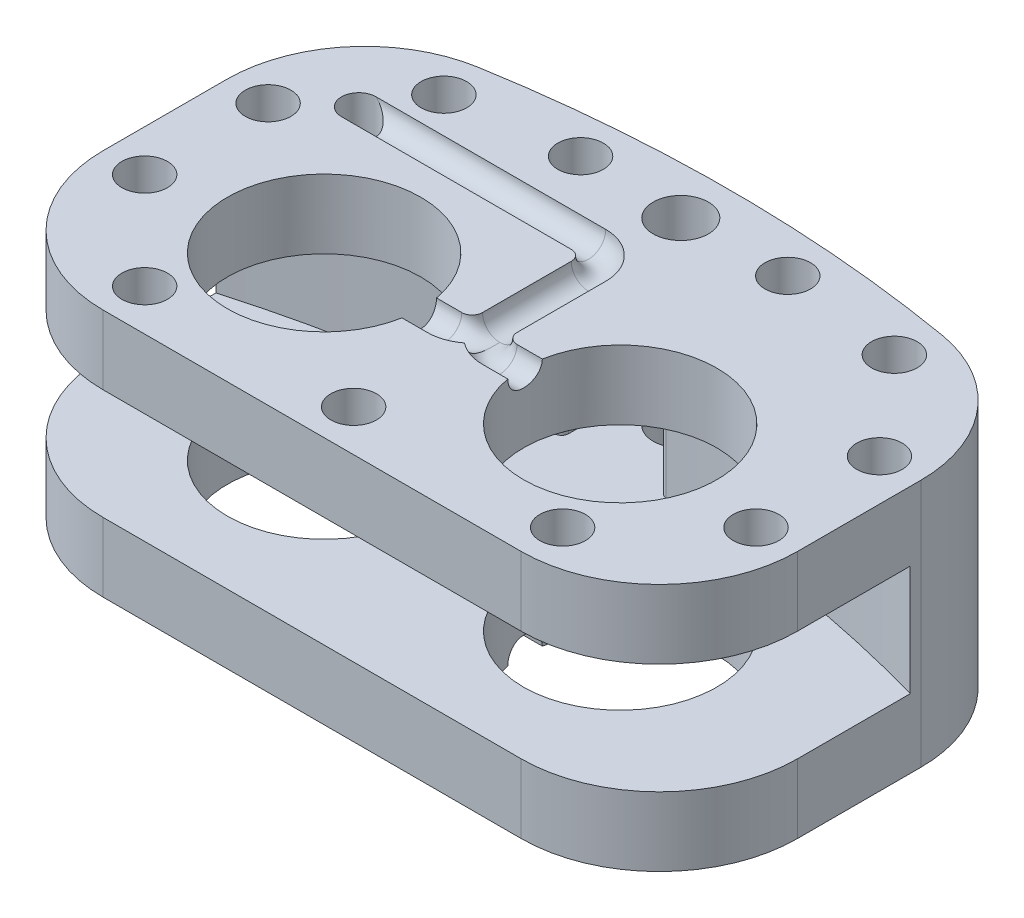
SolidWorks part; units mm, degrees
material "Plain Carbon Steel"
ref_plane "Front Plane" through (0, 0, 0) normal (0, 0, 1) x (1, 0, 0)
ref_plane "Top Plane" through (0, 0, 0) normal (0, 1, 0) x (1, 0, 0)
ref_plane "Right Plane" through (0, 0, 0) normal (1, 0, 0) x (0, 0, -1)
sketch "Sketch1" plane through (0, 0, 0) normal (0, 1, 0) x (1, 0, 0)
  line L0 (0, 0) -> (0, 99.9694) construction
  line L1 (-23.2937, 86.9333) -> (-19.2044, 71.6717) construction
  line L2 (23.2937, 86.9333) -> (19.2044, 71.6717) construction
  line L3 (-25.1276, 87.9821) -> (-20.261, 69.8196) construction
  line L4 (25.1276, 87.9821) -> (20.261, 69.8196) construction
  line L5 (2.4998, 91.4658) -> (2.4998, 94) construction
  line L6 (-2.5, 91.4658) -> (-2.5, 94.0002) construction
  circle A0 centre (0, 0) radius 90 construction
  circle A1 centre (0, 0) radius 74.2 construction
  arc A2 (23.2937, 86.9333) -> (-23.2937, 86.9333) centre (0, 0) ccw construction
  arc A3 (19.2044, 71.6717) -> (-19.2044, 71.6717) centre (0, 0) ccw construction
  arc A4 (25.1276, 87.9821) -> (2.4998, 91.4658) centre (0, 0) ccw construction
  arc A5 (20.261, 69.8196) -> (-20.261, 69.8196) centre (0, 0) ccw construction
  arc A6 (2.4998, 94) -> (-2.5, 94.0002) centre (0, 96.5) ccw construction
  arc A7 (-2.5, 91.4658) -> (-25.1276, 87.9821) centre (0, 0) ccw construction
  arc A8 (25.1276, 87.9821) -> (-25.1276, 87.9821) centre (0, 0) ccw construction
  circle A9 centre (0, 0) radius 91.5 construction
  point P7 (0, 74.2)
  point P18 (0, 91.5)
  point P26 (0, 96.5)
  dimension "D1" = 180
  dimension "D2" = 148.4
  dimension "D5" = 2.5
  dimension "D3" = 15
  dimension "D6" = 2.5
  dimension "D7" = 2.5
  dimension "D8" = 5
  dimension "D4" = 1.5
sketch "Sketch2" plane through (0, 0, 0) normal (0, 1, 0) x (1, 0, 0)
  line L1 (-25.1276, 69.8196) -> (25.1276, 69.8196)
  line L4 (25.1276, 96.8281) -> (25.1276, 69.8196)
  line L5 (-25.1276, 96.8281) -> (-25.1276, 69.8196)
  circle A1 centre (0, 0) radius 100.0354 construction
  arc A4 (2.4998, 94) -> (-2.5, 94.0002) centre (0, 96.5) ccw construction
  arc A5 (-25.1276, 96.8281) -> (25.1276, 96.8281) centre (0, 0) cw
  point P5 (0.0002, 100.0354)
extrude "Boss-Extrude1" add sketch "Sketch2" along normal blind 5
sketch "Sketch3" plane through (0, 5, 0) normal (0, 1, 0) x (1, 0, 0)
  line L0 (-11.7474, 89.23) -> (-9.685, 73.5652) construction
  line L1 (0, -200000) -> (0, 200099.9694) construction
  line L3 (0, -105.3445) -> (0, 105.3445) construction
  circle A0 centre (-10.7162, 81.3976) radius 6.9 construction
  circle A1 centre (0, 0) radius 74.2 construction
  circle A2 centre (0, 0) radius 90 construction
  circle A3 centre (10.7162, 81.3976) radius 6.9 construction
  point P9 (-9.8156, 74.5567)
  point P12 (-9.685, 73.5652)
  point P16 (-11.6168, 88.2386)
  dimension "D1" = 7.5
  dimension "D2" = 1
  dimension "D3" = 1
sketch "Sketch4" plane through (0, 5, 0) normal (0, 1, 0) x (1, 0, 0)
  point P0 (-10.7162, 81.3976)
  point P3 (10.7162, 81.3976)
hole_wizard "Ø12.0mm Dowel Hole1" positions "Sketch4" profile "Sketch5" hole size "Ø12.0" standard "ANSI Metric" end condition through all
sketch "Sketch5" plane through (-10.7162, 5, -81.3976) normal (1, 0, 0) x (0, 0, 1)
  line L0 (0, 0) -> (0, 5)
  line L1 (0, 5) -> (7, 5)
  line L2 (7, 5) -> (7, 0)
  line L5 (7, 0) -> (0, 0)
  line L11 (0, -6.35) -> (0, 107.95) construction
  dimension "Thru Hole Dia." = 14
  dimension "Thru Hole Depth" = 5
sketch "Sketch6" plane through (0, 5, 0) normal (0, 1, 0) x (1, 0, 0)
  line L0 (-3.5354, 91.4317) -> (-3.5354, 99.9729)
  line L1 (3.5354, 91.4317) -> (3.5354, 99.9729)
  line L2 (25.1276, 87.9821) -> (25.1276, 96.8281)
  line L3 (-25.1276, 87.9821) -> (-25.1276, 96.8281)
  arc A0 (-2.5, 91.4658) -> (-25.1276, 87.9821) centre (0, 0) ccw construction
  arc A1 (25.1276, 96.8281) -> (-25.1276, 96.8281) centre (0, 0) ccw construction
  arc A2 (25.1276, 87.9821) -> (2.4998, 91.4658) centre (0, 0) ccw construction
  arc A3 (2.4998, 94) -> (-2.5, 94.0002) centre (0, 96.5) ccw construction
  arc A4 (-25.1276, 96.8281) -> (-3.5354, 99.9729) centre (0, 0) cw
  arc A5 (3.5354, 99.9729) -> (25.1276, 96.8281) centre (0, 0) cw
  arc A6 (-25.1276, 87.9821) -> (-3.5354, 91.4317) centre (0, 0) cw
  arc A7 (3.5354, 91.4317) -> (25.1276, 87.9821) centre (0, 0) cw
extrude "Boss-Extrude2" add sketch "Sketch6" along normal blind 4
sketch "Sketch7" plane through (0, 5, 0) normal (0, 1, 0) x (1, 0, 0)
  point P0 (0, 96.5)
hole_wizard "Ø4.0mm Dowel Hole1" positions "Sketch7" profile "Sketch8" hole size "Ø4.0" standard "ANSI Metric" end condition through all
sketch "Sketch8" plane through (0, 5, -96.5) normal (1, 0, 0) x (0, 0, 1)
  line L0 (0, 0) -> (0, 5)
  line L1 (0, 5) -> (2, 5)
  line L2 (2, 5) -> (2, 0)
  line L5 (2, 0) -> (0, 0)
  line L11 (0, -6.35) -> (0, 107.95) construction
  dimension "Thru Hole Dia." = 4
  dimension "Thru Hole Depth" = 5
sketch "Sketch9" plane through (0, 0, 0) normal (0, -1, 0) x (1, 0, 0)
  line L0 (-2, -81.3976) -> (-10.7162, -81.3976)
  line L1 (0, -83.3976) -> (0, -89.8196)
  line L2 (-2, -91.8196) -> (-18.6276, -91.8196)
  line L4 (-25.1276, -69.8196) -> (25.1276, -69.8196) construction
  line L5 (-25.1276, -96.8281) -> (-25.1276, -69.8196) construction
  arc A0 (0, -89.8196) -> (-2, -91.8196) centre (-2, -89.8196) cw
  arc A1 (0, -83.3976) -> (-2, -81.3976) centre (-2, -83.3976) ccw
  point P4 (10.7162, -81.3976)
  point P11 (-10.7162, -81.3976)
  dimension "D3" = 2
  dimension "D1" = 22
  dimension "D2" = 6.5
sketch3d "3DSketch1"
  line L0 (-18.6276, 0, -91.8196) -> (-2, 0, -91.8196)
  line L1 (0, 0, -89.8196) -> (0, 0, -83.3976)
  line L2 (2, 0, -81.3976) -> (10.7162, 0, -81.3976)
  line L3 (0, 0, -83.3976) -> (0, 0, -89.8196) construction
  line L4 (-18.6276, 0, -91.8196) -> (-18.6276, 9, -91.8196)
  line L5 (-18.6276, 9, -91.8196) -> (-25.1276, 9, -96.8281)
  arc A0 (0, 0, -83.3976) -> (2, 0, -81.3976) centre (2, 0, -83.3976) ccw
  arc A1 (-2, 0, -91.8196) -> (0, 0, -89.8196) centre (-2, 0, -89.8196) ccw
  point P0 (-13.6276, 0, -91.8196)
  point P14 (0, 0, -81.3976)
  point P15 (2, 2, -83.3976)
  point P18 (0, 0, -91.8196)
  point P19 (-2, -2, -89.8196)
  dimension "D1" = 2
  dimension "D2" = 5
ref_plane "Plane3" through (-13.6276, 0, 0) normal (1, 0, 0) x (0, 0, -1)
sketch "Sketch13" plane through (-13.6276, 0, 0) normal (1, 0, 0) x (0, 0, -1)
  line L1 (83.3976, 0) -> (89.8196, 0) construction
  line L2 (69.8196, 0) -> (96.8281, 0) construction
  circle A0 centre (91.8196, 0) radius 1.25
  point P8 (91.8196, 0)
  dimension "D1" = 2.5
sweep "Cut-Sweep6" cut profiles "Sketch13" path "3DSketch1"
sweep "Cut-Sweep7" cut profiles "Sketch13<4>" path "Sketch9"
sketch "Sketch13<4>" plane through (-13.6276, 0, 0) normal (1, 0, 0) x (0, 0, -1) same geometry as "Sketch13"
ref_plane "Plane2" through (0, 9, 0) normal (0, 1, 0) x (1, 0, 0)
mirror "Mirror5" about plane through (0, 9, 0) normal (0, 1, 0) of "Boss-Extrude2"
mirror "Mirror6" about plane through (0, 9, 0) normal (0, 1, 0) of "Ø4.0mm Dowel Hole1", "Ø12.0mm Dowel Hole1", "Boss-Extrude1", "Cut-Sweep7", "Cut-Sweep6"
ref_plane "Plane4" through (-25.1276, 9, -96.8281) normal (-0.7921, 0, -0.6104) x (-0.6104, 0, 0.7921)
sketch "Sketch16" plane through (-25.1276, 9, -96.8281) normal (-0.7921, 0, -0.6104) x (-0.6104, 0, 0.7921)
  point P0 (0, 0)
hole_wizard "M4x0.7 Tapped Hole2" positions "Sketch16" profile "Sketch17" tap size "M4x0.7" standard "ANSI Metric"
cosmetic thread "Hole Thread32" parameters "D1"=7, "D2"=4
sketch "Sketch17" plane through (-25.1276, 9, -96.8281) normal (0, 1, 0) x (-0.6104, 0, 0.7921)
  line L0 (0, 0) -> (0, 8.9914)
  line L1 (0, 8.9914) -> (1.65, 8)
  line L2 (1.65, 8) -> (1.65, 0)
  line L5 (1.65, 0) -> (0, 0)
  line L10 (0, 8.9914) -> (-1.65, 8) construction
  line L11 (0, -6.35) -> (0, 107.95) construction
  dimension "Tap Drill Dia." = 3.3
  dimension "Tap Drill Depth" = 8
  dimension "Drill Angle" = 118
fillet "Fillet1" radius 10 7 edges at (-25.1276, 2.5, -69.8196) (25.1276, 2.5, -69.8196) (25.1276, 9, -96.8281) (-25.1276, 3.675, -96.8281) (-25.1276, 15.5, -69.8196) (25.1276, 15.5, -69.8196) (-25.1276, 14.325, -96.8281)
sketch "Sketch11" plane through (0, 0, 0) normal (0, -1, 0) x (1, 0, 0)
  line L0 (15.1276, -69.8196) -> (-15.1276, -69.8196) construction
  line L1 (-25.1276, -79.8196) -> (-25.1276, -88.7554) construction
  line L3 (25.1276, -79.8196) -> (25.1276, -88.7554) construction
  line L5 (25.1276, -79.8196) -> (25.1276, -88.7554) construction
  line L6 (15.1276, -72.8196) -> (-15.1276, -72.8196) construction
  line L7 (-22.1276, -79.8196) -> (-22.1276, -88.7554) construction
  line L8 (22.1276, -79.8196) -> (22.1276, -88.7554) construction
  arc A1 (25.1276, -79.8196) -> (15.1276, -69.8196) centre (15.1276, -79.8196) ccw construction
  arc A2 (16.8078, -98.6132) -> (25.1276, -88.7554) centre (15.1276, -88.7554) ccw construction
  arc A3 (-25.1276, -79.8196) -> (-15.1276, -69.8196) centre (-15.1276, -79.8196) cw construction
  arc A4 (15.1276, -69.8196) -> (25.1276, -79.8196) centre (15.1276, -79.8196) cw construction
  arc A5 (-25.1276, -88.7554) -> (-16.8078, -98.6132) centre (-15.1276, -88.7554) ccw construction
  arc A6 (25.1276, -88.7554) -> (16.8078, -98.6132) centre (15.1276, -88.7554) cw construction
  arc A7 (-16.8078, -98.6132) -> (16.8078, -98.6132) centre (0, 0) ccw construction
  arc A8 (-22.1276, -79.8196) -> (-15.1276, -72.8196) centre (-15.1276, -79.8196) cw construction
  arc A9 (-22.1276, -88.7554) -> (-16.3038, -95.6559) centre (-15.1276, -88.7554) ccw construction
  arc A10 (-16.3038, -95.6559) -> (16.3038, -95.6559) centre (0, 0) ccw construction
  arc A11 (22.1276, -88.7554) -> (16.3038, -95.6559) centre (15.1276, -88.7554) cw construction
  arc A12 (15.1276, -72.8196) -> (22.1276, -79.8196) centre (15.1276, -79.8196) cw construction
  point P40 (0, -72.8196)
  point P42 (-15.1276, -72.8196)
  point P43 (15.1276, -72.8196)
  point P44 (22.1276, -79.8196)
  point P45 (22.1276, -88.7554)
  point P46 (16.3038, -95.6559)
  point P47 (-16.3038, -95.6559)
  point P48 (-22.1276, -88.7554)
  point P49 (-22.1276, -79.8196)
  point P50 (-7.5, -96.7451)
  point P52 (7.5, -96.7451)
  dimension "D3" = 97.0354
  dimension "D4" = 7
  dimension "D2" = 15
  dimension "D1" = 3
hole_wizard "M4x0.7 Tapped Hole1" positions "Sketch11" profile "Sketch12" tap size "M4x0.7" standard "ANSI Metric"
sketch "Sketch12" plane through (7.5, 0, -96.7451) normal (1, 0, 0) x (0, 0, -1)
  line L0 (0, 0) -> (0, 3.4914)
  line L1 (0, 3.4914) -> (1.65, 2.5)
  line L2 (1.65, 2.5) -> (1.65, 0)
  line L5 (1.65, 0) -> (0, 0)
  line L10 (0, 3.4914) -> (-1.65, 2.5) construction
  line L11 (0, -6.35) -> (0, 107.95) construction
  dimension "Tap Drill Dia." = 3.3
  dimension "Tap Drill Depth" = 2.5
  dimension "Drill Angle" = 118
cosmetic thread "Hole Thread1" parameters "D1"=2.5, "D2"=4
cosmetic thread "Hole Thread2" parameters "D1"=2.5, "D2"=4
cosmetic thread "Hole Thread3" parameters "D1"=2.5, "D2"=4
cosmetic thread "Hole Thread4" parameters "D1"=2.5, "D2"=4
cosmetic thread "Hole Thread5" parameters "D1"=2.5, "D2"=4
cosmetic thread "Hole Thread6" parameters "D1"=2.5, "D2"=4
cosmetic thread "Hole Thread7" parameters "D1"=2.5, "D2"=4
cosmetic thread "Hole Thread8" parameters "D1"=2.5, "D2"=4
cosmetic thread "Hole Thread9" parameters "D1"=2.5, "D2"=4
cosmetic thread "Hole Thread19" parameters "D1"=2.5, "D2"=4
cosmetic thread "Hole Thread20" parameters "D1"=2.5, "D2"=4
mirror "Mirror7" about plane through (0, 9, 0) normal (0, 1, 0) of "M4x0.7 Tapped Hole1"
cosmetic thread "Hole Thread21" parameters "D1"=2.5, "D2"=4
cosmetic thread "Hole Thread22" parameters "D1"=2.5, "D2"=4
cosmetic thread "Hole Thread23" parameters "D1"=2.5, "D2"=4
cosmetic thread "Hole Thread24" parameters "D1"=2.5, "D2"=4
cosmetic thread "Hole Thread25" parameters "D1"=2.5, "D2"=4
cosmetic thread "Hole Thread26" parameters "D1"=2.5, "D2"=4
cosmetic thread "Hole Thread27" parameters "D1"=2.5, "D2"=4
cosmetic thread "Hole Thread28" parameters "D1"=2.5, "D2"=4
cosmetic thread "Hole Thread29" parameters "D1"=2.5, "D2"=4
cosmetic thread "Hole Thread30" parameters "D1"=2.5, "D2"=4
cosmetic thread "Hole Thread31" parameters "D1"=2.5, "D2"=4
fillet "Fillet2" radius 0.5 2 edges at (-3.5354, 9, -91.4317) (3.5354, 9, -91.4317)
